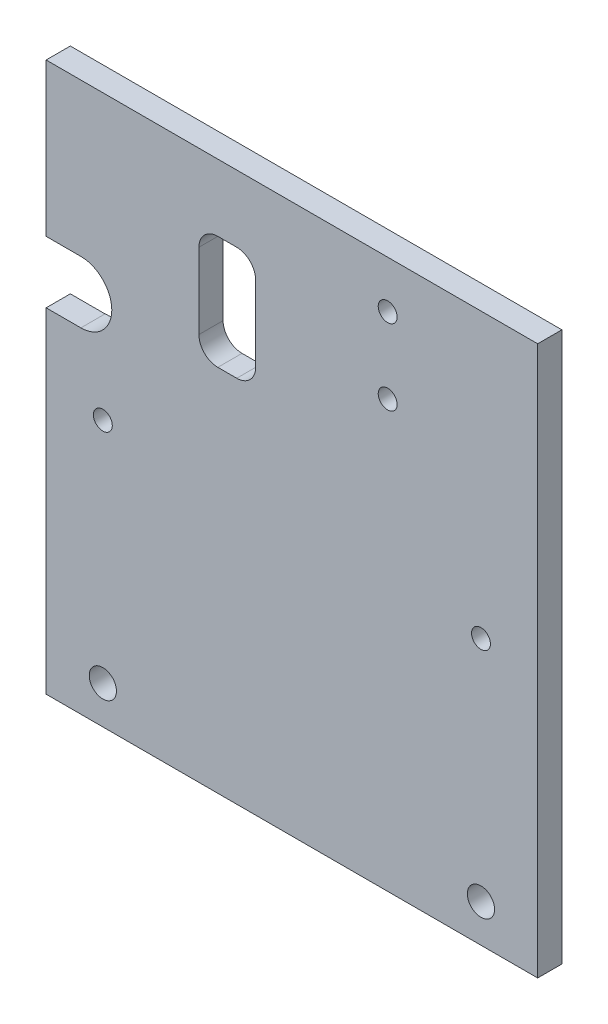
SolidWorks part; units mm, degrees
ref_plane "Front Plane" through (0, 0, 0) normal (0, 0, 1) x (1, 0, 0)
ref_plane "Top Plane" through (0, 0, 0) normal (0, 1, 0) x (1, 0, 0)
ref_plane "Right Plane" through (0, 0, 0) normal (1, 0, 0) x (0, 0, -1)
sketch "Sketch1" plane through (0, 0, 0) normal (0, 0, 1) x (1, 0, 0)
  line L5 (0, 0) -> (100, 0) construction
  line L6 (0, 0) -> (0, 60.26) construction
  line L7 (0, 60.26) -> (100, 60.26) construction
  line L8 (100, 0) -> (100, 60.26) construction
  line L9 (0, 0) -> (100, 60.26) construction
  line L10 (0, 60.26) -> (100, 0) construction
  line L11 (-15, -10) -> (115, -10)
  line L12 (-15, -10) -> (-15, 135.26)
  line L13 (-15, 135.26) -> (115, 135.26)
  line L14 (115, -10) -> (115, 135.26)
  line L15 (-15, -10) -> (115, 135.26) construction
  line L16 (-15, 135.26) -> (115, -10) construction
  circle A0 centre (0, 0) radius 3.6
  circle A1 centre (0, 60.26) radius 2.5
  circle A2 centre (100, 60.26) radius 2.5
  circle A3 centre (100, 0) radius 3.6
  point P6 (50, 30.13)
  point P16 (50, 62.63)
  dimension "D1" = 7.2
  dimension "D3" = 5
  dimension "D2" = 60.26
  dimension "D4" = 100
  dimension "D5" = 15
  dimension "D6" = 15
  dimension "D7" = 10
  dimension "D8" = 75
extrude "Boss-Extrude1" add sketch "Sketch1" along normal blind 6.4
sketch "Sketch2" plane through (0, 0, 6.4) normal (0, 0, 1) x (1, 0, 0)
  circle A2 centre (75.33, 122.7664) radius 2.5
  circle A3 centre (75.33, 102.7664) radius 2.5
  dimension "D1" = 5
  dimension "D2" = 5
extrude "Cut-Extrude1" cut sketch "Sketch2" against normal through all
sketch "Sketch3" plane through (0, 0, 0) normal (0, 0, -1) x (-1, 0, 0)
  line L1 (-35.4075, 117.5704) -> (-30.4075, 117.5704)
  line L2 (-40.4075, 112.5704) -> (-40.4075, 92.5704)
  line L3 (-35.4075, 87.5704) -> (-30.4075, 87.5704)
  line L4 (-25.4075, 112.5704) -> (-25.4075, 92.5704)
  line L5 (-40.4075, 117.5704) -> (-25.4075, 87.5704) construction
  line L6 (-40.4075, 87.5704) -> (-25.4075, 117.5704) construction
  arc A0 (-25.4075, 92.5704) -> (-30.4075, 87.5704) centre (-30.4075, 92.5704) cw
  arc A1 (-35.4075, 87.5704) -> (-40.4075, 92.5704) centre (-35.4075, 92.5704) cw
  arc A2 (-40.4075, 112.5704) -> (-35.4075, 117.5704) centre (-35.4075, 112.5704) cw
  arc A3 (-30.4075, 117.5704) -> (-25.4075, 112.5704) centre (-30.4075, 112.5704) cw
  point P4 (-32.9075, 102.5704)
  dimension "D1" = 5
  dimension "D2" = 30
  dimension "D3" = 15
extrude "Cut-Extrude2" cut sketch "Sketch3" against normal through all
sketch "Sketch4" plane through (0, 0, 6.4) normal (0, 0, 1) x (1, 0, 0)
  line L1 (-15, 135.26) -> (-15, -10) construction
  line L4 (-15, 78.5) -> (-15, 94.86)
  line L5 (-15, 94.86) -> (-5.81, 94.86)
  line L6 (-15, 78.5) -> (-5.81, 78.5)
  line L8 (115, 135.26) -> (-15, 135.26) construction
  arc A2 (-5.81, 94.86) -> (-5.81, 78.5) centre (-5.81, 86.68) cw
  dimension "D1" = 9.19
  dimension "D2" = 16.36
  dimension "D3" = 40.4
extrude "Cut-Extrude3" cut sketch "Sketch4" against normal through all
